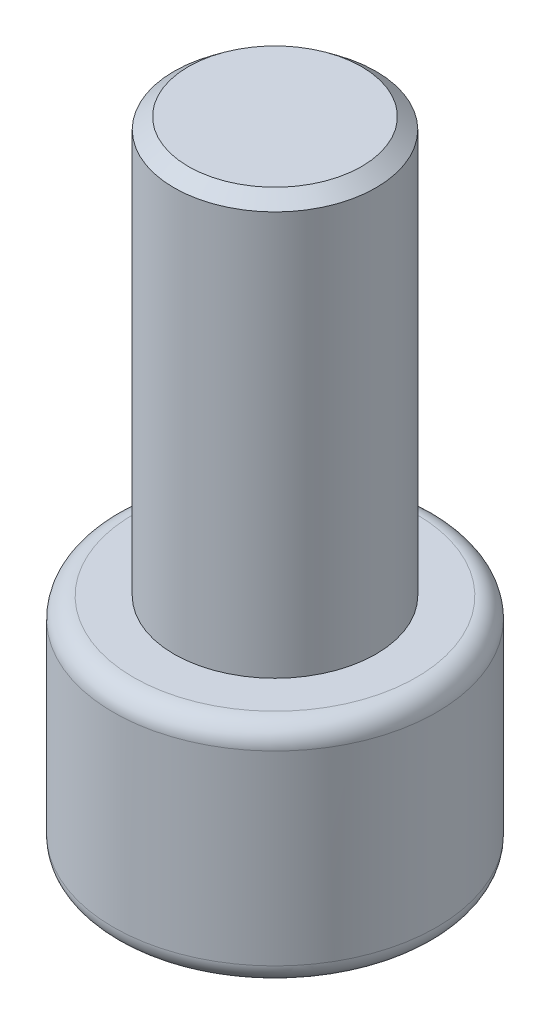
SolidWorks part; units mm, degrees
material "AISI 1020"
ref_plane "Alzado" through (0, 0, 0) normal (0, 0, 1) x (1, 0, 0)
ref_plane "Planta" through (0, 0, 0) normal (0, 1, 0) x (1, 0, 0)
ref_plane "Vista lateral" through (0, 0, 0) normal (1, 0, 0) x (0, 0, -1)
sketch "Croquis1" plane through (0, 0, 0) normal (0, 0, 1) x (1, 0, 0)
  line L0 (0, 0) -> (0, 85.9498) construction
  line L1 (-5, 31.2164) -> (-5, 11.2164)
  line L2 (-5, 11.2164) -> (-15.9235, 2.682) construction
  line L3 (-15, 0) -> (0, 0) construction
  line L4 (-15, 0) -> (-15, 5.5806) construction
  line L5 (-15.9235, 2.682) -> (-8, -7.4596) construction
  line L6 (-5, 31.2164) -> (-4.2883, 31.7724)
  line L7 (-4.2883, 31.7724) -> (0, 31.7724)
  line L8 (-5, 31.2164) -> (1.4006, 31.2164) construction
  line L9 (0, 0) -> (0, 31.7724)
  line L10 (-5, 11.2164) -> (-8, 11.2164)
  line L11 (-8, 11.2164) -> (-8, 0)
  line L12 (-8, 0) -> (0, 0)
  arc A0 (-15.9235, 2.682) -> (-15, 0) centre (-15, 1.5) ccw construction
  point P10 (-15, 1.5)
  dimension "D2" = 1.5
  dimension "D5" = 8
  dimension "D1" = 38
  dimension "D3" = 15
  dimension "D4" = 5
  dimension "D6" = 20
  dimension "D7" = 38
  dimension "D8" = 4.2883
revolve "Revolución2" add sketch "Croquis1" angle 360 about L0 region at (-3.1976, 14.0717, 0)
sketch "Croquis2" plane through (0, 0, 0) normal (0, -1, 0) x (1, 0, 0)
  line L1 (0, 5.1962) -> (-4.5, 2.5981)
  line L2 (-4.5, 2.5981) -> (-4.5, -2.5981)
  line L3 (-4.5, -2.5981) -> (0, -5.1962)
  line L4 (0, -5.1962) -> (4.5, -2.5981)
  line L5 (4.5, -2.5981) -> (4.5, 2.5981)
  line L6 (4.5, 2.5981) -> (0, 5.1962)
  circle A0 centre (0, 0) radius 4.5 construction
  dimension "D1" = 9
extrude "Cortar-Extruir1" cut sketch "Croquis2" against normal blind 7
fillet "Redondeo1" radius 1 2 edges at (0, 0, -8) (0, 11.2164, -8)
